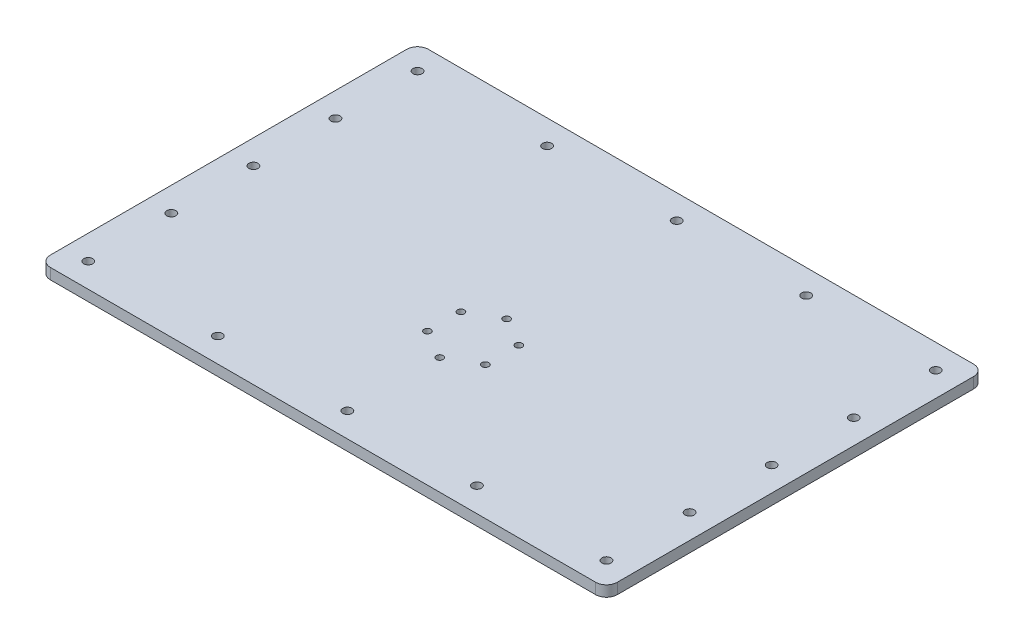
SolidWorks part; units mm, degrees
ref_plane "Front Plane" through (0, 0, 0) normal (0, 0, 1) x (1, 0, 0)
ref_plane "Top Plane" through (0, 0, 0) normal (0, 1, 0) x (1, 0, 0)
ref_plane "Right Plane" through (0, 0, 0) normal (1, 0, 0) x (0, 0, -1)
sketch "Sketch1" plane through (0, 0, 0) normal (0, 1, 0) x (1, 0, 0)
  line L0 (-240, 152.5) -> (-240, -152.5) construction
  line L1 (-252.5, 175) -> (252.5, 175)
  line L2 (-262.5, 165) -> (-262.5, -165)
  line L3 (-252.5, -175) -> (252.5, -175)
  line L4 (262.5, 165) -> (262.5, -165)
  line L5 (-262.5, 175) -> (262.5, -175) construction
  line L6 (-262.5, -175) -> (262.5, 175) construction
  line L7 (-240, -152.5) -> (240, -152.5) construction
  line L8 (240, 152.5) -> (240, -152.5) construction
  line L9 (-240, 152.5) -> (240, 152.5) construction
  line L10 (-262.5, -175) -> (262.5, -175) construction
  line L11 (-262.5, 175) -> (-262.5, -175) construction
  line L12 (262.5, 175) -> (262.5, -175) construction
  line L13 (-262.5, 175) -> (262.5, 175) construction
  line L14 (0, -5) -> (0, 175) construction
  line L15 (0, -5) -> (0, -36) construction
  circle A0 centre (-240, 152.5) radius 4.2
  circle A1 centre (-240, 76.5) radius 4.2
  circle A2 centre (-240, 0.5) radius 4.2
  circle A3 centre (-240, -75.5) radius 4.2
  circle A6 centre (240, 152.5) radius 4.2
  circle A7 centre (240, 76.5) radius 4.2
  circle A8 centre (240, 0.5) radius 4.2
  circle A9 centre (240, -75.5) radius 4.2
  arc A12 (-252.5, -175) -> (-262.5, -165) centre (-252.5, -165) cw
  arc A13 (252.5, -175) -> (262.5, -165) centre (252.5, -165) ccw
  arc A14 (262.5, 165) -> (252.5, 175) centre (252.5, 165) ccw
  arc A15 (-262.5, 165) -> (-252.5, 175) centre (-252.5, 165) cw
  circle A16 centre (0, -5) radius 3.2
  circle A22 centre (-120, 152.5) radius 4.2
  circle A23 centre (0, 152.5) radius 4.2
  circle A24 centre (120, 152.5) radius 4.2
  circle A26 centre (26.8468, -20.5) radius 3.2
  circle A27 centre (26.8468, -51.5) radius 3.2
  circle A28 centre (0, -67) radius 3.2
  circle A29 centre (-26.8468, -51.5) radius 3.2
  circle A30 centre (-26.8468, -20.5) radius 3.2
  circle A31 centre (-240, -152.5) radius 4.2
  circle A32 centre (-120, -152.5) radius 4.2
  circle A33 centre (0, -152.5) radius 4.2
  circle A34 centre (120, -152.5) radius 4.2
  circle A35 centre (240, -152.5) radius 4.2
  point P0 (0, 0)
  point P65 (0, -36)
  dimension "D4" = 4
  dimension "D5" = 4
  dimension "D6" = 10
  dimension "D7" = 6
  dimension "D11" = 5
  dimension "D1" = 525
  dimension "D2" = 350
  dimension "D9" = 180
  dimension "D10" = 31
  dimension "D3" = 22.5
  dimension "D8" = 4
base flange "Base-Flange1" sketch "Sketch1" thickness 10 reverse thickness direction yes parameters "D1"=0.7366
sketch "Bend-Lines1" [suppressed] plane through (0, 0, 0) normal (0, 1, 0) x (1, 0, 0)
sketch "Bounding-Box1" [suppressed] plane through (0, 0, 0) normal (0, 1, 0) x (1, 0, 0)
sheet metal parameters "Sheet-Metal5" thickness 10 parameters "D1"=0.7366
flat pattern "Flat-Pattern5" [suppressed]
sketch "Bend-Lines2" plane through (0, 0, 0) normal (0, 1, 0) x (1, 0, 0)
sketch3d "Bounding-Box2" [suppressed]
  line L0 (10, 340, 0) -> (-515, 340, 0) construction
  line L1 (10, -10, 0) -> (-515, -10, 0) construction
  line L2 (10, 340, 0) -> (10, -10, 0) construction
  line L3 (-515, 340, 0) -> (-515, -10, 0) construction
